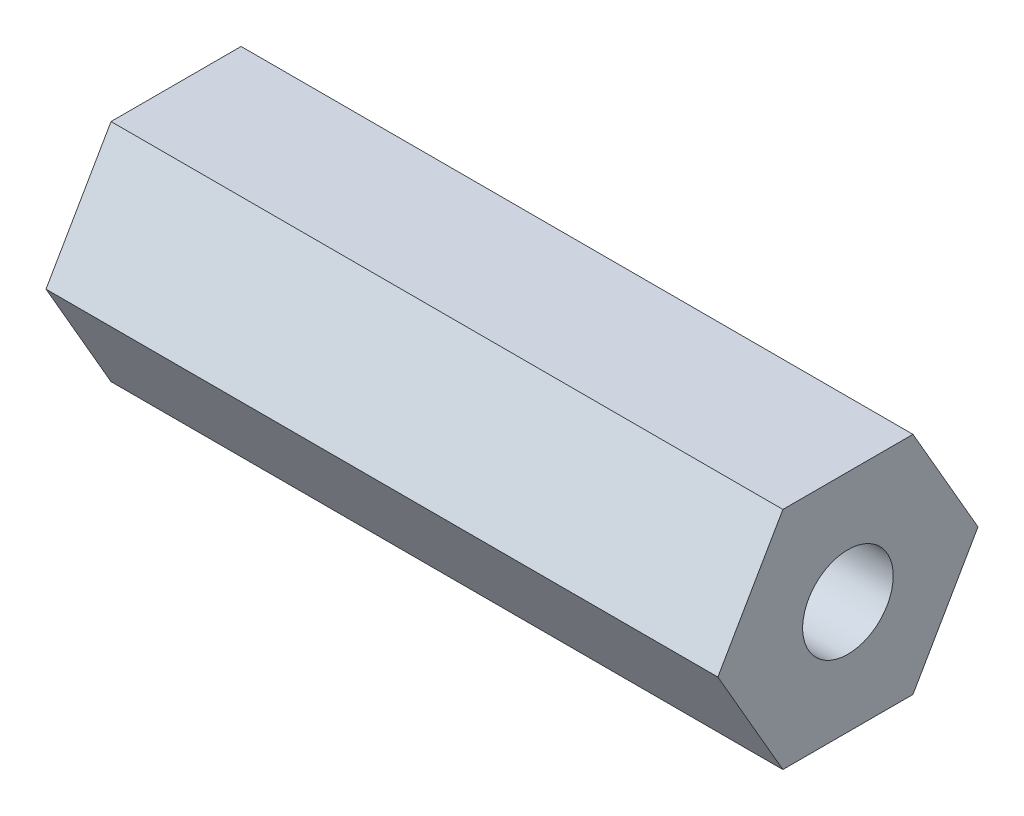
SolidWorks part; units mm, degrees
ref_plane "Front" through (0, 0, 0) normal (0, 0, 1) x (1, 0, 0)
ref_plane "Top" through (0, 0, 0) normal (0, 1, 0) x (1, 0, 0)
ref_plane "Right" through (0, 0, 0) normal (1, 0, 0) x (0, 0, -1)
sketch "Sketch1" plane through (0, 0, 0) normal (1, 0, 0) x (0, 0, -1)
  line L1 (7.3323, 0) -> (3.6662, 6.35)
  line L2 (3.6662, 6.35) -> (-3.6662, 6.35)
  line L3 (-3.6662, 6.35) -> (-7.3323, 0)
  line L4 (-7.3323, 0) -> (-3.6662, -6.35)
  line L5 (-3.6662, -6.35) -> (3.6662, -6.35)
  line L6 (3.6662, -6.35) -> (7.3323, 0)
  circle A0 centre (0, 0) radius 6.35 construction
  dimension "D1" = 12.7
extrude "Boss-Extrude1" add sketch "Sketch1" along normal mid plane 37.875
ref_axis "Axis1" through (-80.9, 0, 0) along (1, 0, 0)
hole_wizard "1/4-20 Tapped Hole1" positions "Sketch2" profile "Sketch3" tap size "1/4-20" standard "ANSI Inch" end condition through all
sketch "Sketch2" plane through (18.9375, 0, 0) normal (1, 0, 0) x (0, 0, -1)
  point P0 (0, 0)
sketch "Sketch3" plane through (18.9375, 0, 0) normal (0, 1, 0) x (0, 0, -1)
  line L0 (0, 0) -> (0, 37.875)
  line L1 (0, 37.875) -> (2.5527, 37.875)
  line L2 (2.5527, 37.875) -> (2.5527, 0)
  line L5 (2.5527, 0) -> (0, 0)
  line L11 (0, -6.35) -> (0, 107.95) construction
  dimension "Thru Tap Drill Dia." = 5.1054
  dimension "Thru Tap Drill Depth" = 37.875
cosmetic thread "Hole Thread1" parameters "D2"=6.35
